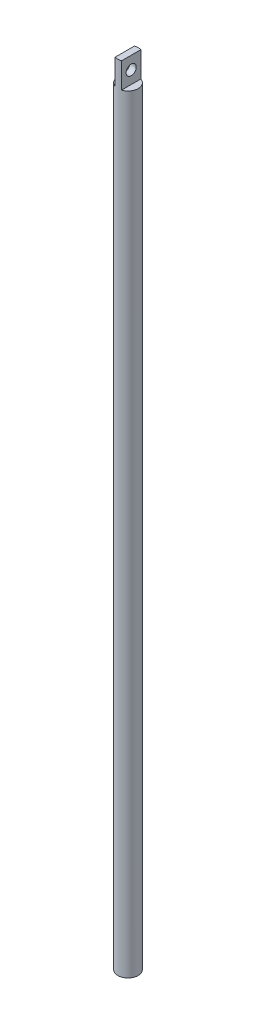
SolidWorks part; units mm, degrees
ref_plane "前视基准面" through (0, 0, 0) normal (0, 0, 1) x (1, 0, 0)
ref_plane "上视基准面" through (0, 0, 0) normal (0, 1, 0) x (1, 0, 0)
ref_plane "右视基准面" through (0, 0, 0) normal (1, 0, 0) x (0, 0, -1)
sketch "草图1" plane through (0, 0, 0) normal (0, 1, 0) x (1, 0, 0)
  circle A0 centre (0, 0) radius 8
  dimension "D1" = 16
extrude "凸台-拉伸1" add sketch "草图1" along normal blind 15
sketch "草图2" plane through (0, 15, 0) normal (0, 1, 0) x (1, 0, 0)
  circle A0 centre (0, 0) radius 8
  dimension "D1" = 16
extrude "凸台-拉伸2" add sketch "草图2" along normal blind 610
sketch "草图3" plane through (0, 625, 0) normal (0, 1, 0) x (1, 0, 0)
  line L1 (-2.5, 10) -> (2.5, 10)
  line L2 (-2.5, 10) -> (-2.5, -10)
  line L3 (-2.5, -10) -> (2.5, -10)
  line L4 (2.5, 10) -> (2.5, -10)
  line L5 (-2.5, 10) -> (2.5, -10) construction
  line L6 (-2.5, -10) -> (2.5, 10) construction
  point P0 (0, 0)
  point P1 (0, 0)
  dimension "D1" = 5
  dimension "D2" = 20
extrude "切除-拉伸1" cut sketch "草图3" against normal blind 20 flip side to cut
ref_plane "基准面1" through (-2.5, 0, 0) normal (-1, 0, 0) x (0, 0, 1)
sketch "草图4" plane through (-2.5, 0, 0) normal (-1, 0, 0) x (0, 0, 1)
  line L0 (0, 0) -> (0, 362.7684) construction
  line L4 (-7.5993, 615) -> (7.5993, 615)
  line L5 (-7.5993, 615) -> (3.3094, 615) construction
  circle A0 centre (0, 615) radius 4
  point P8 (0, 615)
  dimension "D2" = 8
  dimension "D1" = 10
extrude "切除-拉伸2" cut sketch "草图4" against normal blind 20
